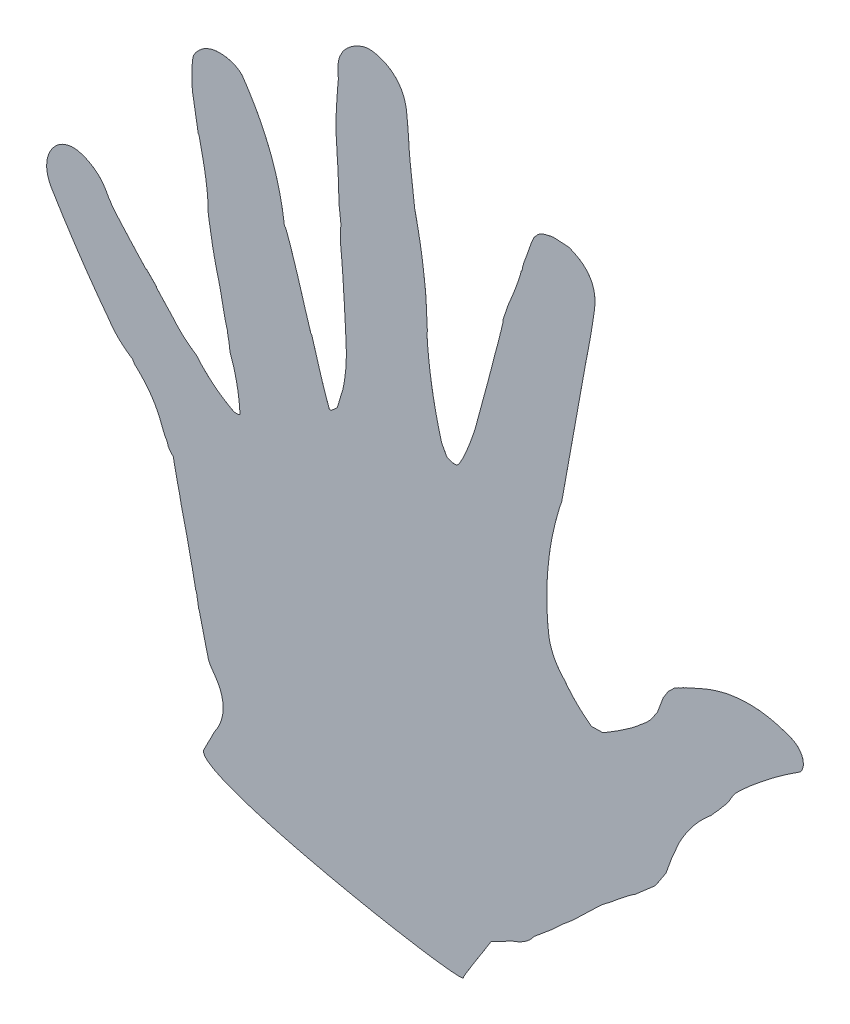
SolidWorks part; units mm, degrees
ref_plane "Plan de face" through (0, 0, 0) normal (0, 0, 1) x (1, 0, 0)
ref_plane "Plan de dessus" through (0, 0, 0) normal (0, 1, 0) x (1, 0, 0)
ref_plane "Plan de droite" through (0, 0, 0) normal (1, 0, 0) x (0, 0, -1)
sketch "Model" plane through (0, 0, 0) normal (0, 0, 1) x (1, 0, 0)
  line L0 (126.0092, -67.0317) -> (126.0337, -67.1279)
  line L1 (126.0337, -67.1279) -> (126.0791, -67.3399)
  line L2 (126.0791, -67.3399) -> (126.1236, -67.4942)
  line L3 (126.1236, -67.4942) -> (126.1236, -67.5328)
  line L4 (126.1236, -67.5328) -> (126.1477, -67.5707)
  line L5 (126.1477, -67.5707) -> (126.1477, -67.5907)
  line L6 (126.1477, -67.5907) -> (126.169, -67.6102)
  line L7 (126.169, -67.6102) -> (126.1477, -67.5707)
  line L8 (126.1477, -67.5707) -> (126.1477, -67.5523)
  line L9 (126.1477, -67.5523) -> (126.1236, -67.5137)
  line L10 (126.1236, -67.5137) -> (126.1236, -67.4942)
  line L11 (126.1236, -67.4942) -> (126.1236, -67.4364)
  line L12 (126.1236, -67.4364) -> (126.0791, -67.3399)
  line L13 (126.0791, -67.3399) -> (126.055, -67.2626)
  line L14 (126.055, -67.2626) -> (126.0092, -67.0317)
  line L15 (180.2508, -38.7148) -> (180.2967, -38.0785)
  line L16 (180.2967, -38.0785) -> (180.3645, -37.4801)
  line L17 (180.3645, -37.4801) -> (180.3893, -36.8825)
  line L18 (180.3893, -36.8825) -> (180.4117, -36.3227)
  line L19 (180.4117, -36.3227) -> (180.3893, -35.7444)
  line L20 (180.3893, -35.7444) -> (180.3645, -35.2046)
  line L21 (180.3645, -35.2046) -> (180.2508, -34.144)
  line L22 (180.2508, -34.144) -> (180.0228, -33.1213)
  line L23 (180.0228, -33.1213) -> (179.8629, -32.6199)
  line L24 (179.8629, -32.6199) -> (179.7258, -32.1567)
  line L25 (179.7258, -32.1567) -> (179.5208, -31.6746)
  line L26 (179.5208, -31.6746) -> (179.3155, -31.231)
  line L27 (179.3155, -31.231) -> (179.0871, -30.7874)
  line L28 (179.0871, -30.7874) -> (178.8594, -30.3826)
  line L29 (178.8594, -30.3826) -> (178.2644, -29.5525)
  line L30 (178.2644, -29.5525) -> (177.9454, -29.1476)
  line L31 (177.9454, -29.1476) -> (177.6257, -28.7814)
  line L32 (177.6257, -28.7814) -> (177.2381, -28.3957)
  line L33 (177.2381, -28.3957) -> (176.8729, -28.0481)
  line L34 (176.8729, -28.0481) -> (176.4623, -27.7008)
  line L35 (176.4623, -27.7008) -> (176.0499, -27.3926)
  line L36 (176.0499, -27.3926) -> (175.571, -27.0642)
  line L37 (175.571, -27.0642) -> (175.1149, -26.7748)
  line L38 (175.1149, -26.7748) -> (174.111, -26.216)
  line L39 (174.111, -26.216) -> (173.0148, -25.6949)
  line L40 (173.0148, -25.6949) -> (172.4212, -25.4439)
  line L41 (172.4212, -25.4439) -> (171.851, -25.2319)
  line L42 (171.851, -25.2319) -> (166.8735, -24.9425)
  line L43 (166.8735, -24.9425) -> (165.9837, -25.1163)
  line L44 (165.9837, -25.1163) -> (165.0483, -25.3282)
  line L45 (165.0483, -25.3282) -> (164.1571, -25.5602)
  line L46 (164.1571, -25.5602) -> (163.7692, -25.6758)
  line L47 (163.7692, -25.6758) -> (163.4498, -25.8103)
  line L48 (163.4498, -25.8103) -> (162.8796, -26.0425)
  line L49 (162.8796, -26.0425) -> (162.6726, -26.1579)
  line L50 (162.6726, -26.1579) -> (162.5127, -26.2928)
  line L51 (162.5127, -26.2928) -> (161.9884, -26.6015)
  line L52 (161.9884, -26.6015) -> (160.7092, -28.0681)
  line L53 (160.7092, -28.0681) -> (160.2528, -29.0511)
  line L54 (160.2528, -29.0511) -> (159.7739, -30.1315)
  line L55 (159.7739, -30.1315) -> (159.5689, -30.672)
  line L56 (159.5689, -30.672) -> (159.3863, -31.1926)
  line L57 (159.3863, -31.1926) -> (159.2037, -31.6746)
  line L58 (159.2037, -31.6746) -> (159.0669, -32.1376)
  line L59 (159.0669, -32.1376) -> (158.9071, -32.5611)
  line L60 (158.9071, -32.5611) -> (158.7703, -32.9668)
  line L61 (158.7703, -32.9668) -> (158.6318, -33.333)
  line L62 (158.6318, -33.333) -> (158.5405, -33.6806)
  line L63 (158.5405, -33.6806) -> (158.4034, -33.9895)
  line L64 (158.4034, -33.9895) -> (158.3125, -34.2787)
  line L65 (158.3125, -34.2787) -> (158.2212, -34.5297)
  line L66 (158.2212, -34.5297) -> (158.1526, -34.7607)
  line L67 (158.1526, -34.7607) -> (158.0617, -34.9539)
  line L68 (158.0617, -34.9539) -> (157.9931, -35.1274)
  line L69 (157.9931, -35.1274) -> (157.9473, -35.2618)
  line L70 (157.9473, -35.2618) -> (157.9246, -35.378)
  line L71 (157.9246, -35.378) -> (157.5139, -36.3811)
  line L72 (157.5139, -36.3811) -> (157.1945, -37.4036)
  line L73 (157.1945, -37.4036) -> (156.921, -38.4445)
  line L74 (156.921, -38.4445) -> (156.7611, -39.5056)
  line L75 (156.7611, -39.5056) -> (156.5317, -39.545)
  line L76 (156.5317, -39.545) -> (156.4645, -39.7759)
  line L77 (156.4645, -39.7759) -> (156.396, -40.0651)
  line L78 (156.396, -40.0651) -> (156.3033, -40.3732)
  line L79 (156.3033, -40.3732) -> (156.2347, -40.721)
  line L80 (156.2347, -40.721) -> (156.121, -41.0679)
  line L81 (156.121, -41.0679) -> (156.0067, -41.4543)
  line L82 (156.0067, -41.4543) -> (155.8699, -41.8596)
  line L83 (155.8699, -41.8596) -> (155.7559, -42.3218)
  line L84 (155.7559, -42.3218) -> (155.5733, -42.766)
  line L85 (155.5733, -42.766) -> (155.4138, -43.2671)
  line L86 (155.4138, -43.2671) -> (155.2312, -43.7689)
  line L87 (155.2312, -43.7689) -> (155.0486, -44.3275)
  line L88 (155.0486, -44.3275) -> (154.8205, -44.8875)
  line L89 (154.8205, -44.8875) -> (154.6152, -45.4849)
  line L90 (154.6152, -45.4849) -> (154.3627, -46.1033)
  line L91 (154.3627, -46.1033) -> (154.1346, -46.7586)
  line L92 (154.1346, -46.7586) -> (153.6099, -48.032)
  line L93 (153.6099, -48.032) -> (153.108, -49.2857)
  line L94 (153.108, -49.2857) -> (152.606, -50.462)
  line L95 (152.606, -50.462) -> (152.1258, -51.6194)
  line L96 (152.1258, -51.6194) -> (150.6199, -56.2298)
  line L97 (150.6199, -56.2298) -> (150.6427, -56.8275)
  line L98 (150.6427, -56.8275) -> (150.5059, -57.3095)
  line L99 (150.5059, -57.3095) -> (150.3691, -57.9076)
  line L100 (150.3691, -57.9076) -> (150.2778, -58.2355)
  line L101 (150.2778, -58.2355) -> (150.2093, -58.6014)
  line L102 (150.2093, -58.6014) -> (150.0253, -59.4124)
  line L103 (150.0253, -59.4124) -> (149.7972, -60.2804)
  line L104 (149.7972, -60.2804) -> (149.6601, -60.7432)
  line L105 (149.6601, -60.7432) -> (149.5461, -61.2638)
  line L106 (149.5461, -61.2638) -> (149.2725, -62.3442)
  line L107 (149.2725, -62.3442) -> (148.9987, -63.5401)
  line L108 (148.9987, -63.5401) -> (148.8161, -64.1385)
  line L109 (148.8161, -64.1385) -> (148.6566, -64.7938)
  line L110 (148.6566, -64.7938) -> (148.2914, -66.1636)
  line L111 (148.2914, -66.1636) -> (148.0861, -66.8576)
  line L112 (148.0861, -66.8576) -> (147.9038, -67.6102)
  line L113 (147.9038, -67.6102) -> (147.6981, -68.3619)
  line L114 (147.6981, -68.3619) -> (147.5159, -69.1722)
  line L115 (147.5159, -69.1722) -> (147.2861, -69.963)
  line L116 (147.2861, -69.963) -> (147.0808, -70.8115)
  line L117 (147.0808, -70.8115) -> (146.6246, -72.5671)
  line L118 (146.6246, -72.5671) -> (146.3738, -73.4541)
  line L119 (146.3738, -73.4541) -> (146.1458, -74.3998)
  line L120 (146.1458, -74.3998) -> (145.6421, -76.3473)
  line L121 (145.6421, -76.3473) -> (144.57, -80.2444)
  line L122 (144.57, -80.2444) -> (143.5433, -84.0629)
  line L123 (143.5433, -84.0629) -> (143.04, -85.9346)
  line L124 (143.04, -85.9346) -> (142.5381, -87.7859)
  line L125 (142.5381, -87.7859) -> (141.5573, -91.4509)
  line L126 (141.5573, -91.4509) -> (140.7115, -93.9584)
  line L127 (140.7115, -93.9584) -> (139.7992, -96.4661)
  line L128 (139.7992, -96.4661) -> (139.2973, -97.701)
  line L129 (139.2973, -97.701) -> (138.7936, -98.9547)
  line L130 (138.7936, -98.9547) -> (138.2462, -100.1891)
  line L131 (138.2462, -100.1891) -> (137.9723, -100.8059)
  line L132 (137.9723, -100.8059) -> (137.8355, -101.1146)
  line L133 (137.8355, -101.1146) -> (137.7673, -101.2693)
  line L134 (137.7673, -101.2693) -> (137.7215, -101.4429)
  line L135 (137.7215, -101.4429) -> (136.5564, -103.5065)
  line L136 (136.5564, -103.5065) -> (136.2601, -103.8924)
  line L137 (136.2601, -103.8924) -> (136.032, -104.2012)
  line L138 (136.032, -104.2012) -> (135.9176, -104.3161)
  line L139 (135.9176, -104.3161) -> (135.8263, -104.4124)
  line L140 (135.8263, -104.4124) -> (135.735, -104.4904)
  line L141 (135.735, -104.4904) -> (135.6896, -104.5488)
  line L142 (135.6896, -104.5488) -> (135.4615, -104.6253)
  line L143 (135.4615, -104.6253) -> (135.3929, -104.6253)
  line L144 (135.3929, -104.6253) -> (135.3475, -104.6453)
  line L145 (135.3475, -104.6453) -> (135.2562, -104.6832)
  line L146 (135.2562, -104.6832) -> (135.1194, -104.6832)
  line L147 (135.1194, -104.6832) -> (135.0508, -104.6832)
  line L148 (135.0508, -104.6832) -> (135.005, -104.7023)
  line L149 (135.005, -104.7023) -> (134.8686, -104.7023)
  line L150 (134.8686, -104.7023) -> (134.7983, -104.7023)
  line L151 (134.7983, -104.7023) -> (134.7542, -104.7216)
  line L152 (134.7542, -104.7216) -> (134.4562, -104.6832)
  line L153 (134.4562, -104.6832) -> (134.1827, -104.6453)
  line L154 (134.1827, -104.6453) -> (133.8633, -104.5673)
  line L155 (133.8633, -104.5673) -> (133.5436, -104.4708)
  line L156 (133.5436, -104.4708) -> (133.3155, -104.3745)
  line L157 (133.3155, -104.3745) -> (133.1102, -104.2975)
  line L158 (133.1102, -104.2975) -> (132.8822, -104.1818)
  line L159 (132.8822, -104.1818) -> (132.8122, -104.1432)
  line L160 (132.8122, -104.1432) -> (132.7681, -104.1235)
  line L161 (132.7681, -104.1235) -> (132.6755, -104.0853)
  line L162 (132.6755, -104.0853) -> (132.3344, -103.8924)
  line L163 (132.3344, -103.8924) -> (130.6449, -100.7675)
  line L164 (130.6449, -100.7675) -> (129.6855, -97.1026)
  line L165 (129.6855, -97.1026) -> (128.8414, -93.4763)
  line L166 (128.8414, -93.4763) -> (128.0869, -89.8495)
  line L167 (128.0869, -89.8495) -> (127.4479, -86.2812)
  line L168 (127.4479, -86.2812) -> (126.9004, -82.713)
  line L169 (126.9004, -82.713) -> (126.467, -79.1835)
  line L170 (126.467, -79.1835) -> (126.1236, -75.672)
  line L171 (126.1236, -75.672) -> (125.8955, -72.2004)
  line L172 (125.8955, -72.2004) -> (126.055, -71.9691)
  line L173 (126.055, -71.9691) -> (125.5985, -62.652)
  line L174 (125.5985, -62.652) -> (125.3477, -59.9135)
  line L175 (125.3477, -59.9135) -> (125.0511, -57.387)
  line L176 (125.0511, -57.387) -> (124.7317, -54.8795)
  line L177 (124.7317, -54.8795) -> (124.3897, -52.3722)
  line L178 (124.3897, -52.3722) -> (124.0017, -49.8831)
  line L179 (124.0017, -49.8831) -> (123.567, -47.3756)
  line L180 (123.567, -47.3756) -> (123.0879, -44.8875)
  line L181 (123.0879, -44.8875) -> (122.586, -42.399)
  line L182 (122.586, -42.399) -> (122.0596, -39.9306)
  line L183 (122.0596, -39.9306) -> (122.0141, -39.8722)
  line L184 (122.0141, -39.8722) -> (122.0141, -39.8143)
  line L185 (122.0141, -39.8143) -> (121.9929, -39.7759)
  line L186 (121.9929, -39.7759) -> (121.9929, -39.7567)
  line L187 (121.9929, -39.7567) -> (121.9929, -39.718)
  line L188 (121.9929, -39.718) -> (121.9929, -39.6021)
  line L189 (121.9929, -39.6021) -> (121.9457, -39.4486)
  line L190 (121.9457, -39.4486) -> (121.9228, -39.409)
  line L191 (121.9228, -39.409) -> (121.9228, -39.3902)
  line L192 (121.9228, -39.3902) -> (121.9228, -39.3521)
  line L193 (121.9228, -39.3521) -> (121.9228, -39.2743)
  line L194 (121.9228, -39.2743) -> (121.8787, -39.0624)
  line L195 (121.8787, -39.0624) -> (121.8787, -38.8302)
  line L196 (121.8787, -38.8302) -> (121.7647, -37.9625)
  line L197 (121.7647, -37.9625) -> (121.672, -37.1908)
  line L198 (121.672, -37.1908) -> (121.6263, -36.8446)
  line L199 (121.6263, -36.8446) -> (121.5822, -36.4775)
  line L200 (121.5822, -36.4775) -> (121.4894, -35.7062)
  line L201 (121.4894, -35.7062) -> (121.4453, -35.4745)
  line L202 (121.4453, -35.4745) -> (121.4208, -35.3584)
  line L203 (121.4208, -35.3584) -> (121.4208, -35.2618)
  line L204 (121.4208, -35.2618) -> (121.3752, -34.8189)
  line L205 (121.3752, -34.8189) -> (121.2839, -33.8928)
  line L206 (121.2839, -33.8928) -> (121.1471, -32.8509)
  line L207 (121.1471, -32.8509) -> (121.0787, -32.3114)
  line L208 (121.0787, -32.3114) -> (121.0331, -31.7517)
  line L209 (121.0331, -31.7517) -> (120.942, -31.154)
  line L210 (120.942, -31.154) -> (120.8963, -30.8453)
  line L211 (120.8963, -30.8453) -> (120.8734, -30.691)
  line L212 (120.8734, -30.691) -> (120.8734, -30.5556)
  line L213 (120.8734, -30.5556) -> (120.7365, -29.2825)
  line L214 (120.7365, -29.2825) -> (120.5752, -28.1061)
  line L215 (120.5752, -28.1061) -> (120.4614, -26.9875)
  line L216 (120.4614, -26.9875) -> (120.3487, -25.9266)
  line L217 (120.3487, -25.9266) -> (120.2574, -24.9234)
  line L218 (120.2574, -24.9234) -> (120.1663, -23.9395)
  line L219 (120.1663, -23.9395) -> (120.0978, -23.0334)
  line L220 (120.0978, -23.0334) -> (120.0294, -22.1652)
  line L221 (120.0294, -22.1652) -> (120.0065, -21.3551)
  line L222 (120.0065, -21.3551) -> (119.8452, -19.1756)
  line L223 (119.8452, -19.1756) -> (119.6628, -17.0152)
  line L224 (119.6628, -17.0152) -> (119.4577, -14.8551)
  line L225 (119.4577, -14.8551) -> (119.2065, -12.7136)
  line L226 (119.2065, -12.7136) -> (118.9784, -11.6329)
  line L227 (118.9784, -11.6329) -> (118.7046, -10.5723)
  line L228 (118.7046, -10.5723) -> (118.5221, -10.0326)
  line L229 (118.5221, -10.0326) -> (118.317, -9.5307)
  line L230 (118.317, -9.5307) -> (117.8607, -8.5278)
  line L231 (117.8607, -8.5278) -> (117.5184, -7.9299)
  line L232 (117.5184, -7.9299) -> (117.152, -7.3704)
  line L233 (117.152, -7.3704) -> (116.7641, -6.8302)
  line L234 (116.7641, -6.8302) -> (116.3764, -6.3483)
  line L235 (116.3764, -6.3483) -> (115.9201, -5.8463)
  line L236 (115.9201, -5.8463) -> (115.4622, -5.4038)
  line L237 (115.4622, -5.4038) -> (114.983, -4.9783)
  line L238 (114.983, -4.9783) -> (114.5041, -4.5925)
  line L239 (114.5041, -4.5925) -> (113.9565, -4.188)
  line L240 (113.9565, -4.188) -> (113.4091, -3.8408)
  line L241 (113.4091, -3.8408) -> (112.8372, -3.5126)
  line L242 (112.8372, -3.5126) -> (112.2441, -3.2234)
  line L243 (112.2441, -3.2234) -> (111.6054, -2.934)
  line L244 (111.6054, -2.934) -> (110.9424, -2.7032)
  line L245 (110.9424, -2.7032) -> (110.2579, -2.4707)
  line L246 (110.2579, -2.4707) -> (109.5735, -2.2977)
  line L247 (109.5735, -2.2977) -> (108.8435, -2.1244)
  line L248 (108.8435, -2.1244) -> (108.1348, -2.028)
  line L249 (108.1348, -2.028) -> (107.4276, -1.9885)
  line L250 (107.4276, -1.9885) -> (106.7432, -2.028)
  line L251 (106.7432, -2.028) -> (106.0571, -2.0848)
  line L252 (106.0571, -2.0848) -> (105.3956, -2.2397)
  line L253 (105.3956, -2.2397) -> (104.734, -2.4324)
  line L254 (104.734, -2.4324) -> (104.0939, -2.7032)
  line L255 (104.0939, -2.7032) -> (103.0671, -3.1654)
  line L256 (103.0671, -3.1654) -> (102.1547, -3.6863)
  line L257 (102.1547, -3.6863) -> (101.3091, -4.2463)
  line L258 (101.3091, -4.2463) -> (100.5563, -4.8436)
  line L259 (100.5563, -4.8436) -> (99.849, -5.4801)
  line L260 (99.849, -5.4801) -> (99.2317, -6.1554)
  line L261 (99.2317, -6.1554) -> (98.6841, -6.869)
  line L262 (98.6841, -6.869) -> (98.2278, -7.6602)
  line L263 (98.2278, -7.6602) -> (97.8173, -8.4505)
  line L264 (97.8173, -8.4505) -> (97.6331, -8.856)
  line L265 (97.6331, -8.856) -> (97.4962, -9.2995)
  line L266 (97.4962, -9.2995) -> (97.2454, -10.1677)
  line L267 (97.2454, -10.1677) -> (97.1086, -11.1127)
  line L268 (97.1086, -11.1127) -> (96.9944, -12.0582)
  line L269 (96.9944, -12.0582) -> (96.9944, -13.0795)
  line L270 (96.9944, -13.0795) -> (96.9944, -13.5813)
  line L271 (96.9944, -13.5813) -> (97.0401, -14.1218)
  line L272 (97.0401, -14.1218) -> (97.1998, -15.2211)
  line L273 (97.1998, -15.2211) -> (96.926, -18.191)
  line L274 (96.926, -18.191) -> (96.7205, -21.162)
  line L275 (96.7205, -21.162) -> (96.5381, -24.0938)
  line L276 (96.5381, -24.0938) -> (96.4241, -27.007)
  line L277 (96.4241, -27.007) -> (96.3555, -28.4341)
  line L278 (96.3555, -28.4341) -> (96.3784, -29.8809)
  line L279 (96.3784, -29.8809) -> (96.4468, -31.3275)
  line L280 (96.4468, -31.3275) -> (96.561, -32.794)
  line L281 (96.561, -32.794) -> (96.6523, -34.3171)
  line L282 (96.6523, -34.3171) -> (96.7434, -35.9182)
  line L283 (96.7434, -35.9182) -> (96.8347, -37.5763)
  line L284 (96.8347, -37.5763) -> (96.9717, -39.3321)
  line L285 (96.9717, -39.3321) -> (96.9944, -40.1805)
  line L286 (96.9944, -40.1805) -> (97.0401, -41.0108)
  line L287 (97.0401, -41.0108) -> (97.0855, -41.8202)
  line L288 (97.0855, -41.8202) -> (97.1327, -42.6115)
  line L289 (97.1327, -42.6115) -> (97.1541, -43.3445)
  line L290 (97.1541, -43.3445) -> (97.1998, -44.0776)
  line L291 (97.1998, -44.0776) -> (97.2225, -44.7716)
  line L292 (97.2225, -44.7716) -> (97.2697, -45.447)
  line L293 (97.2697, -45.447) -> (97.2697, -46.064)
  line L294 (97.2697, -46.064) -> (97.291, -46.6816)
  line L295 (97.291, -46.6816) -> (97.291, -47.2605)
  line L296 (97.291, -47.2605) -> (97.3367, -47.8195)
  line L297 (97.3367, -47.8195) -> (97.3367, -48.34)
  line L298 (97.3367, -48.34) -> (97.3367, -48.8415)
  line L299 (97.3367, -48.8415) -> (97.3367, -49.3047)
  line L300 (97.3367, -49.3047) -> (97.3367, -49.517)
  line L301 (97.3367, -49.517) -> (97.361, -49.7482)
  line L302 (97.361, -49.7482) -> (97.361, -49.8831)
  line L303 (97.361, -49.8831) -> (97.361, -50.0953)
  line L304 (97.361, -50.0953) -> (97.3823, -50.3657)
  line L305 (97.3823, -50.3657) -> (97.428, -50.7323)
  line L306 (97.428, -50.7323) -> (97.4752, -51.1183)
  line L307 (97.4752, -51.1183) -> (97.5191, -51.6005)
  line L308 (97.5191, -51.6005) -> (97.5875, -52.121)
  line L309 (97.5875, -52.121) -> (97.6803, -52.7379)
  line L310 (97.6803, -52.7379) -> (97.7244, -53.3365)
  line L311 (97.7244, -53.3365) -> (97.7473, -53.606)
  line L312 (97.7473, -53.606) -> (97.793, -53.8758)
  line L313 (97.793, -53.8758) -> (97.8402, -54.3579)
  line L314 (97.8402, -54.3579) -> (97.8402, -54.4544)
  line L315 (97.8402, -54.4544) -> (97.8612, -54.5705)
  line L316 (97.8612, -54.5705) -> (97.9084, -54.802)
  line L317 (97.9084, -54.802) -> (97.9084, -54.9761)
  line L318 (97.9084, -54.9761) -> (97.9298, -55.1689)
  line L319 (97.9298, -55.1689) -> (97.9754, -55.4772)
  line L320 (97.9754, -55.4772) -> (97.9754, -55.728)
  line L321 (97.9754, -55.728) -> (97.9754, -55.8245)
  line L322 (97.9754, -55.8245) -> (97.9982, -55.9404)
  line L323 (97.9982, -55.9404) -> (97.9982, -55.9974)
  line L324 (97.9982, -55.9974) -> (97.8612, -57.6182)
  line L325 (97.8612, -57.6182) -> (97.8173, -59.2577)
  line L326 (97.8173, -59.2577) -> (97.8612, -60.8971)
  line L327 (97.8612, -60.8971) -> (98.0211, -62.5555)
  line L328 (98.0211, -62.5555) -> (98.0683, -63.2308)
  line L329 (98.0683, -63.2308) -> (98.1596, -63.9837)
  line L330 (98.1596, -63.9837) -> (98.2052, -64.755)
  line L331 (98.2052, -64.755) -> (98.2963, -65.585)
  line L332 (98.2963, -65.585) -> (98.3418, -66.4332)
  line L333 (98.3418, -66.4332) -> (98.4331, -67.3399)
  line L334 (98.4331, -67.3399) -> (98.5017, -68.2854)
  line L335 (98.5017, -68.2854) -> (98.5928, -69.2881)
  line L336 (98.5928, -69.2881) -> (98.6384, -70.3104)
  line L337 (98.6384, -70.3104) -> (98.7297, -71.3717)
  line L338 (98.7297, -71.3717) -> (98.7981, -72.4705)
  line L339 (98.7981, -72.4705) -> (98.8894, -73.647)
  line L340 (98.8894, -73.647) -> (98.9349, -74.8239)
  line L341 (98.9349, -74.8239) -> (99.0262, -76.0775)
  line L342 (99.0262, -76.0775) -> (99.1175, -77.3514)
  line L343 (99.1175, -77.3514) -> (99.2088, -78.6817)
  line L344 (99.2088, -78.6817) -> (99.2544, -79.9934)
  line L345 (99.2544, -79.9934) -> (99.3455, -81.2856)
  line L346 (99.3455, -81.2856) -> (99.3912, -82.5395)
  line L347 (99.3912, -82.5395) -> (99.4825, -83.7932)
  line L348 (99.4825, -83.7932) -> (99.5297, -84.989)
  line L349 (99.5297, -84.989) -> (99.5526, -85.5681)
  line L350 (99.5526, -85.5681) -> (99.5967, -86.166)
  line L351 (99.5967, -86.166) -> (99.6423, -87.3041)
  line L352 (99.6423, -87.3041) -> (99.6423, -87.5745)
  line L353 (99.6423, -87.5745) -> (99.6423, -87.7089)
  line L354 (99.6423, -87.7089) -> (99.6666, -87.8637)
  line L355 (99.6666, -87.8637) -> (99.7105, -88.4421)
  line L356 (99.7105, -88.4421) -> (99.7352, -89.2905)
  line L357 (99.7352, -89.2905) -> (99.7352, -89.7149)
  line L358 (99.7352, -89.7149) -> (99.7352, -89.9273)
  line L359 (99.7352, -89.9273) -> (99.7577, -90.1587)
  line L360 (99.7577, -90.1587) -> (99.7791, -91.8561)
  line L361 (99.7791, -91.8561) -> (99.7352, -92.6855)
  line L362 (99.7352, -92.6855) -> (99.7105, -93.5345)
  line L363 (99.7105, -93.5345) -> (99.6423, -95.1932)
  line L364 (99.6423, -95.1932) -> (99.4597, -96.8132)
  line L365 (99.4597, -96.8132) -> (99.2544, -98.4725)
  line L366 (99.2544, -98.4725) -> (98.9805, -100.1312)
  line L367 (98.9805, -100.1312) -> (98.6598, -101.8284)
  line L368 (98.6598, -101.8284) -> (98.4789, -102.3304)
  line L369 (98.4789, -102.3304) -> (96.8118, -107.9242)
  line L370 (96.8118, -107.9242) -> (94.8256, -109.6405)
  line L371 (94.8256, -109.6405) -> (94.5748, -109.66)
  line L372 (94.5748, -109.66) -> (94.4151, -109.6405)
  line L373 (94.4151, -109.6405) -> (94.301, -109.5826)
  line L374 (94.301, -109.5826) -> (94.2325, -109.5055)
  line L375 (94.2325, -109.5055) -> (94.0501, -109.0621)
  line L376 (94.0501, -109.0621) -> (93.8904, -108.5994)
  line L377 (93.8904, -108.5994) -> (93.708, -108.0775)
  line L378 (93.708, -108.0775) -> (93.5238, -107.5574)
  line L379 (93.5238, -107.5574) -> (93.2958, -106.9787)
  line L380 (93.2958, -106.9787) -> (93.1132, -106.3811)
  line L381 (93.1132, -106.3811) -> (92.8851, -105.7443)
  line L382 (92.8851, -105.7443) -> (92.6796, -105.0878)
  line L383 (92.6796, -105.0878) -> (92.543, -104.7216)
  line L384 (92.543, -104.7216) -> (92.4288, -104.3745)
  line L385 (92.4288, -104.3745) -> (92.2007, -103.6223)
  line L386 (92.2007, -103.6223) -> (91.9269, -102.8314)
  line L387 (91.9269, -102.8314) -> (91.6988, -102.0413)
  line L388 (91.6988, -102.0413) -> (91.4251, -101.1919)
  line L389 (91.4251, -101.1919) -> (91.1496, -100.3238)
  line L390 (91.1496, -100.3238) -> (90.8759, -99.4172)
  line L391 (90.8759, -99.4172) -> (90.6022, -98.4725)
  line L392 (90.6022, -98.4725) -> (88.5021, -91.4318)
  line L393 (88.5021, -91.4318) -> (88.2739, -91.3353)
  line L394 (88.2739, -91.3353) -> (87.6122, -89.2138)
  line L395 (87.6122, -89.2138) -> (86.9964, -87.2269)
  line L396 (86.9964, -87.2269) -> (86.4016, -85.3168)
  line L397 (86.4016, -85.3168) -> (85.8771, -83.5234)
  line L398 (85.8771, -83.5234) -> (85.3522, -81.8065)
  line L399 (85.3522, -81.8065) -> (84.8732, -80.2246)
  line L400 (84.8732, -80.2246) -> (84.4155, -78.7201)
  line L401 (84.4155, -78.7201) -> (84.0049, -77.3314)
  line L402 (84.0049, -77.3314) -> (83.5927, -76.0775)
  line L403 (83.5927, -76.0775) -> (83.2292, -74.9201)
  line L404 (83.2292, -74.9201) -> (82.8642, -73.8208)
  line L405 (82.8642, -73.8208) -> (82.5431, -72.7987)
  line L406 (82.5431, -72.7987) -> (82.2237, -71.8146)
  line L407 (82.2237, -71.8146) -> (81.9273, -70.9275)
  line L408 (81.9273, -70.9275) -> (81.6536, -70.0982)
  line L409 (81.6536, -70.0982) -> (81.4024, -69.3465)
  line L410 (81.4024, -69.3465) -> (81.1516, -68.6316)
  line L411 (81.1516, -68.6316) -> (80.9236, -67.9962)
  line L412 (80.9236, -67.9962) -> (80.7181, -67.4172)
  line L413 (80.7181, -67.4172) -> (80.5357, -66.9353)
  line L414 (80.5357, -66.9353) -> (80.3517, -66.4719)
  line L415 (80.3517, -66.4719) -> (80.1936, -66.1052)
  line L416 (80.1936, -66.1052) -> (80.0551, -65.7968)
  line L417 (80.0551, -65.7968) -> (79.9412, -65.585)
  line L418 (79.9412, -65.585) -> (79.6916, -65.4492)
  line L419 (79.6916, -65.4492) -> (79.348, -63.0382)
  line L420 (79.348, -63.0382) -> (78.96, -60.6854)
  line L421 (78.96, -60.6854) -> (78.481, -58.332)
  line L422 (78.481, -58.332) -> (77.9548, -56.0365)
  line L423 (77.9548, -56.0365) -> (77.3388, -53.7409)
  line L424 (77.3388, -53.7409) -> (76.6773, -51.4842)
  line L425 (76.6773, -51.4842) -> (75.9244, -49.2278)
  line L426 (75.9244, -49.2278) -> (75.1244, -47.0283)
  line L427 (75.1244, -47.0283) -> (74.212, -44.81)
  line L428 (74.212, -44.81) -> (73.2522, -42.6501)
  line L429 (73.2522, -42.6501) -> (72.2257, -40.4897)
  line L430 (72.2257, -40.4897) -> (71.1521, -38.3877)
  line L431 (71.1521, -38.3877) -> (69.9885, -36.2844)
  line L432 (69.9885, -36.2844) -> (68.755, -34.2205)
  line L433 (68.755, -34.2205) -> (67.4548, -32.1567)
  line L434 (67.4548, -32.1567) -> (66.1074, -30.1506)
  line L435 (66.1074, -30.1506) -> (65.6725, -29.6681)
  line L436 (65.6725, -29.6681) -> (65.2162, -29.2633)
  line L437 (65.2162, -29.2633) -> (64.7142, -28.8969)
  line L438 (64.7142, -28.8969) -> (64.1895, -28.5691)
  line L439 (64.1895, -28.5691) -> (63.6192, -28.2799)
  line L440 (63.6192, -28.2799) -> (63.0017, -28.0288)
  line L441 (63.0017, -28.0288) -> (62.3628, -27.8167)
  line L442 (62.3628, -27.8167) -> (61.7013, -27.6429)
  line L443 (61.7013, -27.6429) -> (60.8118, -27.45)
  line L444 (60.8118, -27.45) -> (59.966, -27.3348)
  line L445 (59.966, -27.3348) -> (59.122, -27.2767)
  line L446 (59.122, -27.2767) -> (58.3463, -27.2767)
  line L447 (58.3463, -27.2767) -> (57.5465, -27.3151)
  line L448 (57.5465, -27.3151) -> (56.8165, -27.4312)
  line L449 (56.8165, -27.4312) -> (56.0848, -27.5859)
  line L450 (56.0848, -27.5859) -> (55.4004, -27.8167)
  line L451 (55.4004, -27.8167) -> (54.6933, -28.0681)
  line L452 (54.6933, -28.0681) -> (54.053, -28.3957)
  line L453 (54.053, -28.3957) -> (53.4143, -28.7617)
  line L454 (53.4143, -28.7617) -> (52.8211, -29.2055)
  line L455 (52.8211, -29.2055) -> (52.2264, -29.6881)
  line L456 (52.2264, -29.6881) -> (51.6788, -30.2278)
  line L457 (51.6788, -30.2278) -> (51.1314, -30.8255)
  line L458 (51.1314, -30.8255) -> (50.6524, -31.5007)
  line L459 (50.6524, -31.5007) -> (50.1961, -32.2917)
  line L460 (50.1961, -32.2917) -> (50.0593, -32.8319)
  line L461 (50.0593, -32.8319) -> (49.9437, -33.4688)
  line L462 (49.9437, -33.4688) -> (49.8524, -34.144)
  line L463 (49.8524, -34.144) -> (49.7854, -34.9155)
  line L464 (49.7854, -34.9155) -> (49.7157, -35.7251)
  line L465 (49.7157, -35.7251) -> (49.6927, -36.6317)
  line L466 (49.6927, -36.6317) -> (49.67, -37.5963)
  line L467 (49.67, -37.5963) -> (49.6927, -38.6374)
  line L468 (49.6927, -38.6374) -> (49.6927, -39.6603)
  line L469 (49.6927, -39.6603) -> (49.7398, -40.6632)
  line L470 (49.7398, -40.6632) -> (49.7854, -41.589)
  line L471 (49.7854, -41.589) -> (49.8524, -42.4953)
  line L472 (49.8524, -42.4953) -> (51.7474, -53.4712)
  line L473 (51.7474, -53.4712) -> (51.9526, -53.5866)
  line L474 (51.9526, -53.5866) -> (52.2736, -55.0912)
  line L475 (52.2736, -55.0912) -> (52.593, -56.5571)
  line L476 (52.593, -56.5571) -> (52.7298, -57.2511)
  line L477 (52.7298, -57.2511) -> (52.7982, -57.5987)
  line L478 (52.7982, -57.5987) -> (52.8881, -57.9658)
  line L479 (52.8881, -57.9658) -> (53.0262, -58.6407)
  line L480 (53.0262, -58.6407) -> (53.0493, -58.7947)
  line L481 (53.0493, -58.7947) -> (53.0948, -58.9685)
  line L482 (53.0948, -58.9685) -> (53.1861, -59.3161)
  line L483 (53.1861, -59.3161) -> (53.2317, -59.6244)
  line L484 (53.2317, -59.6244) -> (53.2545, -59.7786)
  line L485 (53.2545, -59.7786) -> (53.3001, -59.9514)
  line L486 (53.3001, -59.9514) -> (53.4369, -60.5889)
  line L487 (53.4369, -60.5889) -> (53.6667, -61.8038)
  line L488 (53.6667, -61.8038) -> (53.758, -62.3826)
  line L489 (53.758, -62.3826) -> (53.8704, -62.9612)
  line L490 (53.8704, -62.9612) -> (53.9633, -63.5202)
  line L491 (53.9633, -63.5202) -> (54.0074, -63.7909)
  line L492 (54.0074, -63.7909) -> (54.0074, -63.8488)
  line L493 (54.0074, -63.8488) -> (54.0301, -63.9256)
  line L494 (54.0301, -63.9256) -> (54.0773, -64.08)
  line L495 (54.0773, -64.08) -> (54.2826, -65.4689)
  line L496 (54.2826, -65.4689) -> (54.4652, -66.8388)
  line L497 (54.4652, -66.8388) -> (54.5336, -67.4942)
  line L498 (54.5336, -67.4942) -> (54.6247, -68.1691)
  line L499 (54.6247, -68.1691) -> (54.7617, -69.4998)
  line L500 (54.7617, -69.4998) -> (54.853, -70.7731)
  line L501 (54.853, -70.7731) -> (54.8759, -71.3905)
  line L502 (54.8759, -71.3905) -> (54.9215, -72.027)
  line L503 (54.9215, -72.027) -> (54.9672, -73.2424)
  line L504 (54.9672, -73.2424) -> (54.9672, -73.8398)
  line L505 (54.9672, -73.8398) -> (54.9898, -74.4576)
  line L506 (54.9898, -74.4576) -> (56.0166, -80.4945)
  line L507 (56.0166, -80.4945) -> (56.1533, -81.3055)
  line L508 (56.1533, -81.3055) -> (56.2917, -82.0959)
  line L509 (56.2917, -82.0959) -> (56.4272, -82.8485)
  line L510 (56.4272, -82.8485) -> (56.4272, -82.925)
  line L511 (56.4272, -82.925) -> (56.4513, -83.022)
  line L512 (56.4513, -83.022) -> (56.497, -83.2147)
  line L513 (56.497, -83.2147) -> (56.5883, -83.6002)
  line L514 (56.5883, -83.6002) -> (56.7252, -84.3142)
  line L515 (56.7252, -84.3142) -> (56.862, -85.0086)
  line L516 (56.862, -85.0086) -> (56.9989, -85.6644)
  line L517 (56.9989, -85.6644) -> (57.0673, -85.973)
  line L518 (57.0673, -85.973) -> (57.1584, -86.3007)
  line L519 (57.1584, -86.3007) -> (57.2041, -86.5901)
  line L520 (57.2041, -86.5901) -> (57.2726, -86.8991)
  line L521 (57.2726, -86.8991) -> (57.4096, -87.4777)
  line L522 (57.4096, -87.4777) -> (57.6833, -88.5577)
  line L523 (57.6833, -88.5577) -> (57.7746, -89.0592)
  line L524 (57.7746, -89.0592) -> (57.9115, -89.5411)
  line L525 (57.9115, -89.5411) -> (57.9572, -89.753)
  line L526 (57.9572, -89.753) -> (58.0254, -89.9854)
  line L527 (58.0254, -89.9854) -> (58.1639, -90.4286)
  line L528 (58.1639, -90.4286) -> (58.2781, -90.9686)
  line L529 (58.2781, -90.9686) -> (58.4376, -91.5856)
  line L530 (58.4376, -91.5856) -> (58.5959, -92.3)
  line L531 (58.5959, -92.3) -> (58.7797, -93.1099)
  line L532 (58.7797, -93.1099) -> (58.9623, -93.9781)
  line L533 (58.9623, -93.9781) -> (59.1661, -94.942)
  line L534 (59.1661, -94.942) -> (59.3728, -96.0029)
  line L535 (59.3728, -96.0029) -> (59.6239, -97.1605)
  line L536 (59.6239, -97.1605) -> (59.8065, -98.1833)
  line L537 (59.8065, -98.1833) -> (59.8976, -98.6655)
  line L538 (59.8976, -98.6655) -> (60.0117, -99.1666)
  line L539 (60.0117, -99.1666) -> (60.1941, -100.0926)
  line L540 (60.1941, -100.0926) -> (60.2854, -100.5167)
  line L541 (60.2854, -100.5167) -> (60.3326, -100.7289)
  line L542 (60.3326, -100.7289) -> (60.4011, -100.9602)
  line L543 (60.4011, -100.9602) -> (60.5836, -101.7516)
  line L544 (60.5836, -101.7516) -> (60.7661, -102.5033)
  line L545 (60.7661, -102.5033) -> (60.9486, -103.198)
  line L546 (60.9486, -103.198) -> (61.0399, -103.5065)
  line L547 (61.0399, -103.5065) -> (61.0855, -103.6607)
  line L548 (61.0855, -103.6607) -> (61.1082, -103.7375)
  line L549 (61.1082, -103.7375) -> (61.1539, -103.8341)
  line L550 (61.1539, -103.8341) -> (61.1995, -104.2197)
  line L551 (61.1995, -104.2197) -> (61.2452, -104.5867)
  line L552 (61.2452, -104.5867) -> (61.2907, -104.8951)
  line L553 (61.2907, -104.8951) -> (61.3348, -105.1653)
  line L554 (61.3348, -105.1653) -> (61.3348, -105.3581)
  line L555 (61.3348, -105.3581) -> (61.382, -105.5317)
  line L556 (61.382, -105.5317) -> (61.382, -105.6476)
  line L557 (61.382, -105.6476) -> (61.4276, -105.7443)
  line L558 (61.4276, -105.7443) -> (61.4733, -105.9176)
  line L559 (61.4733, -105.9176) -> (61.5189, -106.1298)
  line L560 (61.5189, -106.1298) -> (61.563, -106.3811)
  line L561 (61.563, -106.3811) -> (61.6331, -106.6701)
  line L562 (61.6331, -106.6701) -> (61.6788, -106.9595)
  line L563 (61.6788, -106.9595) -> (61.7242, -107.3257)
  line L564 (61.7242, -107.3257) -> (61.8612, -108.1167)
  line L565 (61.8612, -108.1167) -> (61.9523, -108.9267)
  line L566 (61.9523, -108.9267) -> (62.0434, -109.6787)
  line L567 (62.0434, -109.6787) -> (62.6823, -111.5117)
  line L568 (62.6823, -111.5117) -> (63.2754, -113.3819)
  line L569 (63.2754, -113.3819) -> (63.7789, -115.292)
  line L570 (63.7789, -115.292) -> (64.2352, -117.2793)
  line L571 (64.2352, -117.2793) -> (64.6002, -119.2652)
  line L572 (64.6002, -119.2652) -> (64.8968, -121.3103)
  line L573 (64.8968, -121.3103) -> (65.1263, -123.3742)
  line L574 (65.1263, -123.3742) -> (65.2861, -125.5152)
  line L575 (65.2861, -125.5152) -> (64.9667, -125.8235)
  line L576 (64.9667, -125.8235) -> (63.9597, -125.901)
  line L577 (63.9597, -125.901) -> (63.0718, -125.6702)
  line L578 (63.0718, -125.6702) -> (62.1805, -125.1682)
  line L579 (62.1805, -125.1682) -> (61.3348, -124.6856)
  line L580 (61.3348, -124.6856) -> (59.6696, -123.6445)
  line L581 (59.6696, -123.6445) -> (58.8483, -123.0848)
  line L582 (58.8483, -123.0848) -> (58.071, -122.5257)
  line L583 (58.071, -122.5257) -> (57.2954, -121.9276)
  line L584 (57.2954, -121.9276) -> (56.5654, -121.3488)
  line L585 (56.5654, -121.3488) -> (55.081, -120.0759)
  line L586 (55.081, -120.0759) -> (53.688, -118.7642)
  line L587 (53.688, -118.7642) -> (53.0037, -118.07)
  line L588 (53.0037, -118.07) -> (52.3648, -117.3756)
  line L589 (52.3648, -117.3756) -> (51.1087, -115.9288)
  line L590 (51.1087, -115.9288) -> (50.0137, -115.2147)
  line L591 (50.0137, -115.2147) -> (48.9856, -114.4628)
  line L592 (48.9856, -114.4628) -> (48.0045, -113.6911)
  line L593 (48.0045, -113.6911) -> (47.0678, -112.8999)
  line L594 (47.0678, -112.8999) -> (46.1324, -112.0516)
  line L595 (46.1324, -112.0516) -> (45.2882, -111.1834)
  line L596 (45.2882, -111.1834) -> (44.4428, -110.2959)
  line L597 (44.4428, -110.2959) -> (43.6898, -109.3899)
  line L598 (43.6898, -109.3899) -> (38.1188, -103.4099)
  line L599 (38.1188, -103.4099) -> (38.1188, -103.1401)
  line L600 (38.1188, -103.1401) -> (35.0606, -100.0347)
  line L601 (35.0606, -100.0347) -> (34.7638, -99.9762)
  line L602 (34.7638, -99.9762) -> (32.2285, -97.2378)
  line L603 (32.2285, -97.2378) -> (29.7177, -94.4792)
  line L604 (29.7177, -94.4792) -> (27.2068, -91.6823)
  line L605 (27.2068, -91.6823) -> (24.7416, -88.8664)
  line L606 (24.7416, -88.8664) -> (24.3081, -88.3264)
  line L607 (24.3081, -88.3264) -> (23.9188, -87.8055)
  line L608 (23.9188, -87.8055) -> (23.5309, -87.2653)
  line L609 (23.5309, -87.2653) -> (23.2113, -86.7253)
  line L610 (23.2113, -86.7253) -> (22.9833, -86.455)
  line L611 (22.9833, -86.455) -> (22.8008, -86.1849)
  line L612 (22.8008, -86.1849) -> (22.6183, -85.8954)
  line L613 (22.6183, -85.8954) -> (22.4813, -85.626)
  line L614 (22.4813, -85.626) -> (22.0937, -84.8737)
  line L615 (22.0937, -84.8737) -> (21.706, -84.1987)
  line L616 (21.706, -84.1987) -> (21.2709, -83.5234)
  line L617 (21.2709, -83.5234) -> (20.8375, -82.9055)
  line L618 (20.8375, -82.9055) -> (20.3583, -82.308)
  line L619 (20.3583, -82.308) -> (19.8563, -81.7483)
  line L620 (19.8563, -81.7483) -> (19.3075, -81.2092)
  line L621 (19.3075, -81.2092) -> (18.7601, -80.7267)
  line L622 (18.7601, -80.7267) -> (18.1439, -80.2444)
  line L623 (18.1439, -80.2444) -> (17.5266, -79.8196)
  line L624 (17.5266, -79.8196) -> (16.8648, -79.415)
  line L625 (16.8648, -79.415) -> (16.2033, -79.0479)
  line L626 (16.2033, -79.0479) -> (15.4733, -78.6817)
  line L627 (15.4733, -78.6817) -> (14.7417, -78.3923)
  line L628 (14.7417, -78.3923) -> (13.9661, -78.1032)
  line L629 (13.9661, -78.1032) -> (13.1904, -77.8903)
  line L630 (13.1904, -77.8903) -> (12.3222, -77.6976)
  line L631 (12.3222, -77.6976) -> (11.5009, -77.6206)
  line L632 (11.5009, -77.6206) -> (10.6796, -77.6404)
  line L633 (10.6796, -77.6404) -> (9.8568, -77.7749)
  line L634 (9.8568, -77.7749) -> (9.1267, -77.9298)
  line L635 (9.1267, -77.9298) -> (8.4653, -78.1415)
  line L636 (8.4653, -78.1415) -> (7.8021, -78.3923)
  line L637 (7.8021, -78.3923) -> (7.2089, -78.7201)
  line L638 (7.2089, -78.7201) -> (6.6158, -79.0677)
  line L639 (6.6158, -79.0677) -> (6.0896, -79.4728)
  line L640 (6.0896, -79.4728) -> (5.5666, -79.9161)
  line L641 (5.5666, -79.9161) -> (5.1087, -80.4178)
  line L642 (5.1087, -80.4178) -> (4.3331, -81.3625)
  line L643 (4.3331, -81.3625) -> (3.7157, -82.385)
  line L644 (3.7157, -82.385) -> (3.2837, -83.2726)
  line L645 (3.2837, -83.2726) -> (2.9857, -84.2178)
  line L646 (2.9857, -84.2178) -> (2.712, -85.2978)
  line L647 (2.712, -85.2978) -> (2.6207, -85.8382)
  line L648 (2.6207, -85.8382) -> (2.5978, -86.3971)
  line L649 (2.5978, -86.3971) -> (2.575, -87.4777)
  line L650 (2.575, -87.4777) -> (2.6207, -88.0172)
  line L651 (2.6207, -88.0172) -> (2.712, -88.577)
  line L652 (2.712, -88.577) -> (2.9171, -89.6565)
  line L653 (2.9171, -89.6565) -> (3.2837, -90.7369)
  line L654 (3.2837, -90.7369) -> (3.4876, -91.258)
  line L655 (3.4876, -91.258) -> (3.74, -91.7982)
  line L656 (3.74, -91.7982) -> (4.3558, -92.8787)
  line L657 (4.3558, -92.8787) -> (6.6843, -96.659)
  line L658 (6.6843, -96.659) -> (7.825, -98.5106)
  line L659 (7.825, -98.5106) -> (9.0129, -100.3432)
  line L660 (9.0129, -100.3432) -> (11.3411, -103.9306)
  line L661 (11.3411, -103.9306) -> (11.615, -104.3556)
  line L662 (11.615, -104.3556) -> (11.7517, -104.5673)
  line L663 (11.7517, -104.5673) -> (11.9116, -104.7988)
  line L664 (11.9116, -104.7988) -> (12.506, -105.6862)
  line L665 (12.506, -105.6862) -> (13.6924, -107.422)
  line L666 (13.6924, -107.422) -> (14.833, -109.1194)
  line L667 (14.833, -109.1194) -> (16.0209, -110.7977)
  line L668 (16.0209, -110.7977) -> (18.3494, -114.0768)
  line L669 (18.3494, -114.0768) -> (19.4913, -115.6775)
  line L670 (19.4913, -115.6775) -> (20.6776, -117.2597)
  line L671 (20.6776, -117.2597) -> (21.8199, -118.822)
  line L672 (21.8199, -118.822) -> (23.0062, -120.3656)
  line L673 (23.0062, -120.3656) -> (23.3498, -120.9821)
  line L674 (23.3498, -120.9821) -> (24.0798, -121.8889)
  line L675 (24.0798, -121.8889) -> (24.8784, -122.7954)
  line L676 (24.8784, -122.7954) -> (25.6768, -123.6636)
  line L677 (25.6768, -123.6636) -> (26.5679, -124.4927)
  line L678 (26.5679, -124.4927) -> (27.4578, -125.284)
  line L679 (27.4578, -125.284) -> (28.4172, -126.0361)
  line L680 (28.4172, -126.0361) -> (29.3984, -126.7495)
  line L681 (29.3984, -126.7495) -> (30.4493, -127.4441)
  line L682 (30.4493, -127.4441) -> (30.7001, -127.9071)
  line L683 (30.7001, -127.9071) -> (30.9969, -128.3701)
  line L684 (30.9969, -128.3701) -> (31.339, -128.7942)
  line L685 (31.339, -128.7942) -> (31.7722, -129.2186)
  line L686 (31.7722, -129.2186) -> (32.4356, -129.8363)
  line L687 (32.4356, -129.8363) -> (33.097, -130.4919)
  line L688 (33.097, -130.4919) -> (34.3746, -131.8614)
  line L689 (34.3746, -131.8614) -> (35.5169, -133.2694)
  line L690 (35.5169, -133.2694) -> (36.6134, -134.7546)
  line L691 (36.6134, -134.7546) -> (37.5714, -136.2787)
  line L692 (37.5714, -136.2787) -> (38.4383, -137.8789)
  line L693 (38.4383, -137.8789) -> (39.2155, -139.5184)
  line L694 (39.2155, -139.5184) -> (39.5578, -140.3673)
  line L695 (39.5578, -140.3673) -> (39.8999, -141.2548)
  line L696 (39.8999, -141.2548) -> (40.2878, -142.2776)
  line L697 (40.2878, -142.2776) -> (40.3791, -142.5284)
  line L698 (40.3791, -142.5284) -> (40.4248, -142.6442)
  line L699 (40.4248, -142.6442) -> (40.4248, -142.6628)
  line L700 (40.4248, -142.6628) -> (40.4473, -142.7017)
  line L701 (40.4473, -142.7017) -> (40.493, -142.7789)
  line L702 (40.493, -142.7789) -> (40.5843, -143.01)
  line L703 (40.5843, -143.01) -> (40.6998, -143.2416)
  line L704 (40.6998, -143.2416) -> (40.7212, -143.3191)
  line L705 (40.7212, -143.3191) -> (40.7668, -143.4155)
  line L706 (40.7668, -143.4155) -> (40.858, -143.5888)
  line L707 (40.858, -143.5888) -> (41.0406, -143.8978)
  line L708 (41.0406, -143.8978) -> (41.2016, -144.1676)
  line L709 (41.2016, -144.1676) -> (41.2702, -144.2834)
  line L710 (41.2702, -144.2834) -> (41.3599, -144.4184)
  line L711 (41.3599, -144.4184) -> (41.4984, -144.6499)
  line L712 (41.4984, -144.6499) -> (41.5439, -144.746)
  line L713 (41.5439, -144.746) -> (41.6123, -144.8621)
  line L714 (41.6123, -144.8621) -> (41.7721, -145.2862)
  line L715 (41.7721, -145.2862) -> (41.8634, -145.711)
  line L716 (41.8634, -145.711) -> (41.886, -145.8075)
  line L717 (41.886, -145.8075) -> (41.9316, -145.9039)
  line L718 (41.9316, -145.9039) -> (42.0002, -146.0769)
  line L719 (42.0002, -146.0769) -> (42.0002, -146.1155)
  line L720 (42.0002, -146.1155) -> (42.0002, -146.1351)
  line L721 (42.0002, -146.1351) -> (42.0229, -146.1737)
  line L722 (42.0229, -146.1737) -> (42.0686, -146.2701)
  line L723 (42.0686, -146.2701) -> (42.1599, -146.4241)
  line L724 (42.1599, -146.4241) -> (42.4792, -146.9454)
  line L725 (42.4792, -146.9454) -> (42.8442, -147.4084)
  line L726 (42.8442, -147.4084) -> (43.2108, -147.8132)
  line L727 (43.2108, -147.8132) -> (43.6442, -148.1605)
  line L728 (43.6442, -148.1605) -> (43.7127, -148.5656)
  line L729 (43.7127, -148.5656) -> (43.8023, -149.0476)
  line L730 (43.8023, -149.0476) -> (43.8952, -149.5688)
  line L731 (43.8952, -149.5688) -> (44.0321, -150.1669)
  line L732 (44.0321, -150.1669) -> (44.146, -150.8029)
  line L733 (44.146, -150.8029) -> (44.3058, -151.4974)
  line L734 (44.3058, -151.4974) -> (44.4653, -152.2498)
  line L735 (44.4653, -152.2498) -> (44.6479, -153.0597)
  line L736 (44.6479, -153.0597) -> (44.8305, -153.9858)
  line L737 (44.8305, -153.9858) -> (44.8989, -154.3716)
  line L738 (44.8989, -154.3716) -> (44.9902, -154.7382)
  line L739 (44.9902, -154.7382) -> (45.0586, -155.0848)
  line L740 (45.0586, -155.0848) -> (45.1499, -155.4131)
  line L741 (45.1499, -155.4131) -> (45.1971, -155.7021)
  line L742 (45.1971, -155.7021) -> (45.2882, -155.9729)
  line L743 (45.2882, -155.9729) -> (45.3323, -156.2237)
  line L744 (45.3323, -156.2237) -> (45.4024, -156.4549)
  line L745 (45.4024, -156.4549) -> (45.4024, -156.5317)
  line L746 (45.4024, -156.5317) -> (45.4024, -156.571)
  line L747 (45.4024, -156.571) -> (45.4024, -156.5896)
  line L748 (45.4024, -156.5896) -> (45.4251, -156.6285)
  line L749 (45.4251, -156.6285) -> (45.4692, -156.8018)
  line L750 (45.4692, -156.8018) -> (45.4692, -156.86)
  line L751 (45.4692, -156.86) -> (45.4921, -156.9365)
  line L752 (45.4921, -156.9365) -> (45.5393, -157.0719)
  line L753 (45.5393, -157.0719) -> (45.5834, -157.2266)
  line L754 (45.5834, -157.2266) -> (45.5834, -157.2648)
  line L755 (45.5834, -157.2648) -> (45.6076, -157.2838)
  line L756 (45.6076, -157.2838) -> (46.2008, -160.3895)
  line L757 (46.2008, -160.3895) -> (48.073, -168.3945)
  line L758 (48.073, -168.3945) -> (48.3011, -169.4939)
  line L759 (48.3011, -169.4939) -> (48.3467, -169.7447)
  line L760 (48.3467, -169.7447) -> (48.4151, -170.0148)
  line L761 (48.4151, -170.0148) -> (48.5521, -170.5546)
  line L762 (48.5521, -170.5546) -> (48.6432, -171.0569)
  line L763 (48.6432, -171.0569) -> (48.6888, -171.3077)
  line L764 (48.6888, -171.3077) -> (48.7574, -171.5771)
  line L765 (48.7574, -171.5771) -> (48.9856, -172.5996)
  line L766 (48.9856, -172.5996) -> (49.1681, -173.5643)
  line L767 (49.1681, -173.5643) -> (49.3961, -174.5092)
  line L768 (49.3961, -174.5092) -> (49.5787, -175.416)
  line L769 (49.5787, -175.416) -> (49.67, -175.8597)
  line L770 (49.67, -175.8597) -> (49.7854, -176.3221)
  line L771 (49.7854, -176.3221) -> (49.8068, -176.5157)
  line L772 (49.8068, -176.5157) -> (49.8524, -176.7272)
  line L773 (49.8524, -176.7272) -> (49.9437, -177.1516)
  line L774 (49.9437, -177.1516) -> (50.1275, -177.9619)
  line L775 (50.1275, -177.9619) -> (50.2645, -178.7529)
  line L776 (50.2645, -178.7529) -> (50.2645, -178.8297)
  line L777 (50.2645, -178.8297) -> (50.2874, -178.9262)
  line L778 (50.2874, -178.9262) -> (50.333, -179.1195)
  line L779 (50.333, -179.1195) -> (50.4243, -179.5053)
  line L780 (50.4243, -179.5053) -> (50.5611, -180.2188)
  line L781 (50.5611, -180.2188) -> (50.698, -180.913)
  line L782 (50.698, -180.913) -> (50.8119, -181.5689)
  line L783 (50.8119, -181.5689) -> (50.9488, -182.2052)
  line L784 (50.9488, -182.2052) -> (51.1314, -182.3599)
  line L785 (51.1314, -182.3599) -> (51.8843, -186.9119)
  line L786 (51.8843, -186.9119) -> (52.0454, -187.0663)
  line L787 (52.0454, -187.0663) -> (52.0454, -187.1434)
  line L788 (52.0454, -187.1434) -> (52.0683, -187.2399)
  line L789 (52.0683, -187.2399) -> (52.114, -187.4328)
  line L790 (52.114, -187.4328) -> (52.2037, -187.8187)
  line L791 (52.2037, -187.8187) -> (52.3878, -188.59)
  line L792 (52.3878, -188.59) -> (52.7525, -190.1141)
  line L793 (52.7525, -190.1141) -> (53.4825, -193.0845)
  line L794 (53.4825, -193.0845) -> (53.8019, -194.5315)
  line L795 (53.8019, -194.5315) -> (54.1686, -195.9581)
  line L796 (54.1686, -195.9581) -> (54.5109, -197.3471)
  line L797 (54.5109, -197.3471) -> (54.8759, -198.7358)
  line L798 (54.8759, -198.7358) -> (54.9672, -199.1603)
  line L799 (54.9672, -199.1603) -> (55.104, -199.6044)
  line L800 (55.104, -199.6044) -> (55.2636, -200.0092)
  line L801 (55.2636, -200.0092) -> (55.469, -200.4336)
  line L802 (55.469, -200.4336) -> (55.6743, -200.8191)
  line L803 (55.6743, -200.8191) -> (55.9253, -201.2239)
  line L804 (55.9253, -201.2239) -> (56.1776, -201.6097)
  line L805 (56.1776, -201.6097) -> (56.4741, -202.0149)
  line L806 (56.4741, -202.0149) -> (57.2041, -203.0567)
  line L807 (57.2041, -203.0567) -> (57.8886, -204.0981)
  line L808 (57.8886, -204.0981) -> (58.4376, -205.1399)
  line L809 (58.4376, -205.1399) -> (58.6884, -205.6612)
  line L810 (58.6884, -205.6612) -> (58.9166, -206.201)
  line L811 (58.9166, -206.201) -> (59.2817, -207.2428)
  line L812 (59.2817, -207.2428) -> (59.5554, -208.3032)
  line L813 (59.5554, -208.3032) -> (59.738, -209.345)
  line L814 (59.738, -209.345) -> (59.8291, -210.4251)
  line L815 (59.8291, -210.4251) -> (59.7834, -211.4672)
  line L816 (59.7834, -211.4672) -> (59.738, -212.007)
  line L817 (59.738, -212.007) -> (59.6696, -212.5469)
  line L818 (59.6696, -212.5469) -> (59.4413, -213.5887)
  line L819 (59.4413, -213.5887) -> (59.3046, -214.1285)
  line L820 (59.3046, -214.1285) -> (59.1447, -214.6687)
  line L821 (59.1447, -214.6687) -> (58.7341, -215.7105)
  line L822 (58.7341, -215.7105) -> (58.2323, -216.7902)
  line L823 (58.2323, -216.7902) -> (57.9341, -217.3304)
  line L824 (57.9341, -217.3304) -> (57.6147, -217.8709)
  line L825 (57.6147, -217.8709) -> (56.9304, -218.951)
  line L826 (56.9304, -218.951) -> (55.6972, -221.4204)
  line L827 (55.6972, -221.4204) -> (55.3548, -222.0564)
  line L828 (55.3548, -222.0564) -> (55.0354, -222.6741)
  line L829 (55.0354, -222.6741) -> (54.7389, -223.2332)
  line L830 (54.7389, -223.2332) -> (54.4864, -223.7734)
  line L831 (54.4864, -223.7734) -> (54.2354, -224.2361)
  line L832 (54.2354, -224.2361) -> (54.0074, -224.6798)
  line L833 (54.0074, -224.6798) -> (53.8019, -225.0464)
  line L834 (53.8019, -225.0464) -> (53.6195, -225.4126)
  line L835 (53.6195, -225.4126) -> (53.46, -225.7595)
  line L836 (53.46, -225.7595) -> (53.4143, -226.1454)
  line L837 (53.4143, -226.1454) -> (53.4825, -226.5316)
  line L838 (53.4825, -226.5316) -> (53.688, -226.9367)
  line L839 (53.688, -226.9367) -> (53.9633, -227.3419)
  line L840 (53.9633, -227.3419) -> (54.3724, -227.7856)
  line L841 (54.3724, -227.7856) -> (54.8986, -228.229)
  line L842 (54.8986, -228.229) -> (55.5603, -228.692)
  line L843 (55.5603, -228.692) -> (56.2917, -229.1547)
  line L844 (56.2917, -229.1547) -> (57.1584, -229.6373)
  line L845 (57.1584, -229.6373) -> (58.1167, -230.1189)
  line L846 (58.1167, -230.1189) -> (59.2133, -230.6402)
  line L847 (59.2133, -230.6402) -> (60.4011, -231.1414)
  line L848 (60.4011, -231.1414) -> (61.7013, -231.6816)
  line L849 (61.7013, -231.6816) -> (63.1174, -232.2215)
  line L850 (63.1174, -232.2215) -> (64.6687, -232.781)
  line L851 (64.6687, -232.781) -> (66.0161, -233.2443)
  line L852 (66.0161, -233.2443) -> (67.4321, -233.7067)
  line L853 (67.4321, -233.7067) -> (68.8919, -234.1697)
  line L854 (68.8919, -234.1697) -> (70.4448, -234.6523)
  line L855 (70.4448, -234.6523) -> (72.0204, -235.1154)
  line L856 (72.0204, -235.1154) -> (73.6858, -235.5973)
  line L857 (73.6858, -235.5973) -> (75.3983, -236.0793)
  line L858 (75.3983, -236.0793) -> (77.202, -236.5813)
  line L859 (77.202, -236.5813) -> (79.0286, -237.0629)
  line L860 (79.0286, -237.0629) -> (80.9463, -237.5645)
  line L861 (80.9463, -237.5645) -> (82.9081, -238.0661)
  line L862 (82.9081, -238.0661) -> (84.9416, -238.5674)
  line L863 (84.9416, -238.5674) -> (87.0174, -239.069)
  line L864 (87.0174, -239.069) -> (89.1651, -239.5702)
  line L865 (89.1651, -239.5702) -> (91.3794, -240.0718)
  line L866 (91.3794, -240.0718) -> (93.6623, -240.6124)
  line L867 (93.6623, -240.6124) -> (95.6243, -241.0368)
  line L868 (95.6243, -241.0368) -> (97.5875, -241.4612)
  line L869 (97.5875, -241.4612) -> (98.5473, -241.6538)
  line L870 (98.5473, -241.6538) -> (98.7738, -241.6927)
  line L871 (98.7738, -241.6927) -> (99.0262, -241.7503)
  line L872 (99.0262, -241.7503) -> (99.5297, -241.8657)
  line L873 (99.5297, -241.8657) -> (101.4917, -242.2905)
  line L874 (101.4917, -242.2905) -> (103.4095, -242.676)
  line L875 (103.4095, -242.676) -> (105.3271, -243.0815)
  line L876 (105.3271, -243.0815) -> (105.7834, -243.1586)
  line L877 (105.7834, -243.1586) -> (106.0114, -243.1972)
  line L878 (106.0114, -243.1972) -> (106.2626, -243.2547)
  line L879 (106.2626, -243.2547) -> (107.2222, -243.448)
  line L880 (107.2222, -243.448) -> (109.1172, -243.8335)
  line L881 (109.1172, -243.8335) -> (110.0298, -243.9879)
  line L882 (110.0298, -243.9879) -> (110.4861, -244.0654)
  line L883 (110.4861, -244.0654) -> (110.7156, -244.104)
  line L884 (110.7156, -244.104) -> (110.9665, -244.1615)
  line L885 (110.9665, -244.1615) -> (112.8143, -244.5088)
  line L886 (112.8143, -244.5088) -> (114.6409, -244.8364)
  line L887 (114.6409, -244.8364) -> (116.4902, -245.1833)
  line L888 (116.4902, -245.1833) -> (116.6957, -245.2033)
  line L889 (116.6957, -245.2033) -> (116.9238, -245.2419)
  line L890 (116.9238, -245.2419) -> (117.3799, -245.319)
  line L891 (117.3799, -245.319) -> (118.2941, -245.473)
  line L892 (118.2941, -245.473) -> (120.0978, -245.7814)
  line L893 (120.0978, -245.7814) -> (121.8787, -246.0715)
  line L894 (121.8787, -246.0715) -> (123.6581, -246.3794)
  line L895 (123.6581, -246.3794) -> (125.1881, -246.6113)
  line L896 (125.1881, -246.6113) -> (125.9182, -246.7078)
  line L897 (125.9182, -246.7078) -> (126.6496, -246.8232)
  line L898 (126.6496, -246.8232) -> (128.0201, -247.0161)
  line L899 (128.0201, -247.0161) -> (129.343, -247.2094)
  line L900 (129.343, -247.2094) -> (129.9363, -247.2669)
  line L901 (129.9363, -247.2669) -> (130.5536, -247.3441)
  line L902 (130.5536, -247.3441) -> (130.8275, -247.3634)
  line L903 (130.8275, -247.3634) -> (131.1241, -247.402)
  line L904 (131.1241, -247.402) -> (131.6943, -247.4791)
  line L905 (131.6943, -247.4791) -> (132.745, -247.5949)
  line L906 (132.745, -247.5949) -> (133.7262, -247.7106)
  line L907 (133.7262, -247.7106) -> (134.1827, -247.7299)
  line L908 (134.1827, -247.7299) -> (134.6157, -247.7685)
  line L909 (134.6157, -247.7685) -> (135.0281, -247.7881)
  line L910 (135.0281, -247.7881) -> (135.4157, -247.8264)
  line L911 (135.4157, -247.8264) -> (135.7581, -247.8264)
  line L912 (135.7581, -247.8264) -> (136.0775, -247.8457)
  line L913 (136.0775, -247.8457) -> (136.3741, -247.8457)
  line L914 (136.3741, -247.8457) -> (136.6476, -247.8457)
  line L915 (136.6476, -247.8457) -> (136.8757, -247.8071)
  line L916 (136.8757, -247.8071) -> (137.0828, -247.8071)
  line L917 (137.0828, -247.8071) -> (137.4021, -247.7685)
  line L918 (137.4021, -247.7685) -> (137.5162, -247.7299)
  line L919 (137.5162, -247.7299) -> (137.6074, -247.6913)
  line L920 (137.6074, -247.6913) -> (137.6302, -247.6528)
  line L921 (137.6302, -247.6528) -> (137.676, -247.6335)
  line L922 (137.676, -247.6335) -> (137.7215, -247.5949)
  line L923 (137.7215, -247.5949) -> (137.8586, -247.1512)
  line L924 (137.8586, -247.1512) -> (138.0636, -246.7656)
  line L925 (138.0636, -246.7656) -> (138.2462, -246.4187)
  line L926 (138.2462, -246.4187) -> (138.4742, -246.0522)
  line L927 (138.4742, -246.0522) -> (138.7023, -245.6467)
  line L928 (138.7023, -245.6467) -> (138.9762, -245.2419)
  line L929 (138.9762, -245.2419) -> (139.5481, -244.3162)
  line L930 (139.5481, -244.3162) -> (139.8447, -243.8146)
  line L931 (139.8447, -243.8146) -> (140.1868, -243.3133)
  line L932 (140.1868, -243.3133) -> (140.5062, -242.7535)
  line L933 (140.5062, -242.7535) -> (140.8713, -242.1747)
  line L934 (140.8713, -242.1747) -> (141.2379, -241.577)
  line L935 (141.2379, -241.577) -> (141.6485, -240.9596)
  line L936 (141.6485, -240.9596) -> (142.0361, -240.3037)
  line L937 (142.0361, -240.3037) -> (142.4695, -239.6284)
  line L938 (142.4695, -239.6284) -> (142.9046, -238.9339)
  line L939 (142.9046, -238.9339) -> (143.3838, -238.2204)
  line L940 (143.3838, -238.2204) -> (146.7845, -232.8196)
  line L941 (146.7845, -232.8196) -> (147.6068, -232.3955)
  line L942 (147.6068, -232.3955) -> (148.0175, -232.1829)
  line L943 (148.0175, -232.1829) -> (148.4512, -231.9907)
  line L944 (148.4512, -231.9907) -> (150.0952, -231.1607)
  line L945 (150.0952, -231.1607) -> (151.7151, -230.3122)
  line L946 (151.7151, -230.3122) -> (152.4923, -229.8681)
  line L947 (152.4923, -229.8681) -> (153.2906, -229.444)
  line L948 (153.2906, -229.444) -> (153.9065, -229.2125)
  line L949 (153.9065, -229.2125) -> (154.2045, -229.0964)
  line L950 (154.2045, -229.0964) -> (154.5239, -229)
  line L951 (154.5239, -229) -> (154.7978, -228.8653)
  line L952 (154.7978, -228.8653) -> (155.0941, -228.7492)
  line L953 (155.0941, -228.7492) -> (155.6646, -228.5184)
  line L954 (155.6646, -228.5184) -> (155.9154, -228.3637)
  line L955 (155.9154, -228.3637) -> (156.1893, -228.229)
  line L956 (156.1893, -228.229) -> (156.7153, -227.9585)
  line L957 (156.7153, -227.9585) -> (157.2173, -227.6695)
  line L958 (157.2173, -227.6695) -> (157.7192, -227.3804)
  line L959 (157.7192, -227.3804) -> (157.8105, -227.284)
  line L960 (157.8105, -227.284) -> (157.9246, -227.2065)
  line L961 (157.9246, -227.2065) -> (158.1526, -227.0521)
  line L962 (158.1526, -227.0521) -> (158.2439, -226.9557)
  line L963 (158.2439, -226.9557) -> (158.3579, -226.8788)
  line L964 (158.3579, -226.8788) -> (158.5877, -226.7241)
  line L965 (158.5877, -226.7241) -> (158.9757, -226.3769)
  line L966 (158.9757, -226.3769) -> (159.3863, -226.03)
  line L967 (159.3863, -226.03) -> (159.7284, -225.6438)
  line L968 (159.7284, -225.6438) -> (160.0705, -225.2583)
  line L969 (160.0705, -225.2583) -> (160.3899, -224.8531)
  line L970 (160.3899, -224.8531) -> (160.7092, -224.448)
  line L971 (160.7092, -224.448) -> (162.2165, -223.1943)
  line L972 (162.2165, -223.1943) -> (166.2576, -219.8191)
  line L973 (166.2576, -219.8191) -> (170.002, -216.3468)
  line L974 (170.002, -216.3468) -> (173.1743, -213.6848)
  line L975 (173.1743, -213.6848) -> (182.0771, -205.1206)
  line L976 (182.0771, -205.1206) -> (182.9914, -204.3296)
  line L977 (182.9914, -204.3296) -> (185.0002, -202.7869)
  line L978 (185.0002, -202.7869) -> (185.7761, -202.1889)
  line L979 (185.7761, -202.1889) -> (187.5341, -200.7037)
  line L980 (187.5341, -200.7037) -> (189.3376, -199.276)
  line L981 (189.3376, -199.276) -> (191.1401, -197.868)
  line L982 (191.1401, -197.868) -> (192.9898, -196.5372)
  line L983 (192.9898, -196.5372) -> (193.1948, -196.4986)
  line L984 (193.1948, -196.4986) -> (199.9974, -190.5579)
  line L985 (199.9974, -190.5579) -> (203.4226, -185.3496)
  line L986 (203.4226, -185.3496) -> (205.4545, -179.7751)
  line L987 (205.4545, -179.7751) -> (206.1387, -178.3281)
  line L988 (206.1387, -178.3281) -> (207.1216, -175.9558)
  line L989 (207.1216, -175.9558) -> (207.6459, -174.7986)
  line L990 (207.6459, -174.7986) -> (208.2619, -173.6797)
  line L991 (208.2619, -173.6797) -> (208.8779, -172.5614)
  line L992 (208.8779, -172.5614) -> (209.5641, -171.4807)
  line L993 (209.5641, -171.4807) -> (210.2707, -170.3999)
  line L994 (210.2707, -170.3999) -> (211.0252, -169.3585)
  line L995 (211.0252, -169.3585) -> (212.5993, -167.2956)
  line L996 (212.5993, -167.2956) -> (213.445, -166.2923)
  line L997 (213.445, -166.2923) -> (214.3349, -165.3277)
  line L998 (214.3349, -165.3277) -> (215.2475, -164.3631)
  line L999 (215.2475, -164.3631) -> (216.23, -163.4374)
  line L1000 (216.23, -163.4374) -> (217.2122, -162.511)
  line L1001 (217.2122, -162.511) -> (218.2844, -161.6239)
  line L1002 (218.2844, -161.6239) -> (218.3074, -161.5467)
  line L1003 (218.3074, -161.5467) -> (218.4215, -161.4317)
  line L1004 (218.4215, -161.4317) -> (218.49, -161.3352)
  line L1005 (218.49, -161.3352) -> (218.581, -161.2191)
  line L1006 (218.581, -161.2191) -> (218.695, -161.0844)
  line L1007 (218.695, -161.0844) -> (218.8549, -160.949)
  line L1008 (218.8549, -160.949) -> (219.1515, -160.5635)
  line L1009 (219.1515, -160.5635) -> (219.3337, -160.3509)
  line L1010 (219.3337, -160.3509) -> (219.5618, -160.1387)
  line L1011 (219.5618, -160.1387) -> (219.7688, -159.869)
  line L1012 (219.7688, -159.869) -> (220.0196, -159.5989)
  line L1013 (220.0196, -159.5989) -> (220.2708, -159.3095)
  line L1014 (220.2708, -159.3095) -> (220.5674, -159.0201)
  line L1015 (220.5674, -159.0201) -> (221.1376, -158.3063)
  line L1016 (221.1376, -158.3063) -> (221.4115, -157.9594)
  line L1017 (221.4115, -157.9594) -> (221.7095, -157.6503)
  line L1018 (221.7095, -157.6503) -> (221.9589, -157.323)
  line L1019 (221.9589, -157.323) -> (222.2114, -157.033)
  line L1020 (222.2114, -157.033) -> (222.6903, -156.4742)
  line L1021 (222.6903, -156.4742) -> (223.0782, -155.9529)
  line L1022 (223.0782, -155.9529) -> (223.4434, -155.471)
  line L1023 (223.4434, -155.471) -> (223.7397, -155.0276)
  line L1024 (223.7397, -155.0276) -> (224.0377, -154.6607)
  line L1025 (224.0377, -154.6607) -> (224.3574, -154.0244)
  line L1026 (224.3574, -154.0244) -> (224.7222, -153.4259)
  line L1027 (224.7222, -153.4259) -> (225.0874, -152.8279)
  line L1028 (225.0874, -152.8279) -> (225.5208, -152.2691)
  line L1029 (225.5208, -152.2691) -> (225.9314, -151.7096)
  line L1030 (225.9314, -151.7096) -> (226.412, -151.1887)
  line L1031 (226.412, -151.1887) -> (227.4159, -150.2048)
  line L1032 (227.4159, -150.2048) -> (229.6759, -148.1412)
  line L1033 (229.6759, -148.1412) -> (230.8162, -147.1183)
  line L1034 (230.8162, -147.1183) -> (232.0044, -146.1351)
  line L1035 (232.0044, -146.1351) -> (234.3568, -144.1869)
  line L1036 (234.3568, -144.1869) -> (236.7979, -142.2776)
  line L1037 (236.7979, -142.2776) -> (239.2419, -140.4066)
  line L1038 (239.2419, -140.4066) -> (241.7754, -138.5931)
  line L1039 (241.7754, -138.5931) -> (244.3551, -136.8378)
  line L1040 (244.3551, -136.8378) -> (246.9799, -135.1408)
  line L1041 (246.9799, -135.1408) -> (247.2311, -134.7739)
  line L1042 (247.2311, -134.7739) -> (247.4364, -134.4848)
  line L1043 (247.4364, -134.4848) -> (247.5728, -134.234)
  line L1044 (247.5728, -134.234) -> (247.62, -134.1375)
  line L1045 (247.62, -134.1375) -> (247.6872, -134.0793)
  line L1046 (247.6872, -134.0793) -> (247.7785, -133.7514)
  line L1047 (247.7785, -133.7514) -> (247.8698, -133.4427)
  line L1048 (247.8698, -133.4427) -> (247.9397, -133.1343)
  line L1049 (247.9397, -133.1343) -> (247.9838, -132.8257)
  line L1050 (247.9838, -132.8257) -> (247.9838, -132.0736)
  line L1051 (247.9838, -132.0736) -> (247.8939, -131.3601)
  line L1052 (247.8939, -131.3601) -> (247.8012, -130.9932)
  line L1053 (247.8012, -130.9932) -> (247.6872, -130.6456)
  line L1054 (247.6872, -130.6456) -> (247.5501, -130.299)
  line L1055 (247.5501, -130.299) -> (247.3906, -129.9903)
  line L1056 (247.3906, -129.9903) -> (247.0712, -129.4884)
  line L1057 (247.0712, -129.4884) -> (246.7291, -129.0454)
  line L1058 (246.7291, -129.0454) -> (246.3639, -128.6202)
  line L1059 (246.3639, -128.6202) -> (245.9764, -128.254)
  line L1060 (245.9764, -128.254) -> (245.5426, -127.8881)
  line L1061 (245.5426, -127.8881) -> (245.0851, -127.5988)
  line L1062 (245.0851, -127.5988) -> (244.6063, -127.3283)
  line L1063 (244.6063, -127.3283) -> (244.104, -127.1164)
  line L1064 (244.104, -127.1164) -> (242.2319, -126.4019)
  line L1065 (242.2319, -126.4019) -> (240.4053, -125.8046)
  line L1066 (240.4053, -125.8046) -> (238.5332, -125.3033)
  line L1067 (238.5332, -125.3033) -> (236.7067, -124.9174)
  line L1068 (236.7067, -124.9174) -> (234.8346, -124.6089)
  line L1069 (234.8346, -124.6089) -> (233.8992, -124.4927)
  line L1070 (233.8992, -124.4927) -> (232.9866, -124.4348)
  line L1071 (232.9866, -124.4348) -> (231.1146, -124.3385)
  line L1072 (231.1146, -124.3385) -> (229.288, -124.3578)
  line L1073 (229.288, -124.3578) -> (227.4159, -124.4542)
  line L1074 (227.4159, -124.4542) -> (225.5435, -124.6661)
  line L1075 (225.5435, -124.6661) -> (223.6714, -124.9555)
  line L1076 (223.6714, -124.9555) -> (222.7361, -125.1481)
  line L1077 (222.7361, -125.1481) -> (221.8235, -125.3805)
  line L1078 (221.8235, -125.3805) -> (219.9514, -125.8817)
  line L1079 (219.9514, -125.8817) -> (218.079, -126.4987)
  line L1080 (218.079, -126.4987) -> (216.2066, -127.1933)
  line L1081 (216.2066, -127.1933) -> (214.3349, -128.0228)
  line L1082 (214.3349, -128.0228) -> (213.6049, -128.3312)
  line L1083 (213.6049, -128.3312) -> (212.8504, -128.6788)
  line L1084 (212.8504, -128.6788) -> (212.0518, -129.0261)
  line L1085 (212.0518, -129.0261) -> (211.2305, -129.4315)
  line L1086 (211.2305, -129.4315) -> (210.3851, -129.7971)
  line L1087 (210.3851, -129.7971) -> (209.9744, -129.9707)
  line L1088 (209.9744, -129.9707) -> (209.6093, -130.1633)
  line L1089 (209.6093, -130.1633) -> (208.902, -130.5112)
  line L1090 (208.902, -130.5112) -> (208.2619, -130.8578)
  line L1091 (208.2619, -130.8578) -> (207.6459, -131.1472)
  line L1092 (207.6459, -131.1472) -> (207.3493, -131.2826)
  line L1093 (207.3493, -131.2826) -> (207.0985, -131.4369)
  line L1094 (207.0985, -131.4369) -> (206.6193, -131.7063)
  line L1095 (206.6193, -131.7063) -> (206.3898, -131.8228)
  line L1096 (206.3898, -131.8228) -> (206.2072, -131.9578)
  line L1097 (206.2072, -131.9578) -> (204.1984, -133.8671)
  line L1098 (204.1984, -133.8671) -> (202.5099, -136.5677)
  line L1099 (202.5099, -136.5677) -> (200.6382, -141.5635)
  line L1100 (200.6382, -141.5635) -> (200.0674, -142.4116)
  line L1101 (200.0674, -142.4116) -> (199.9061, -142.6052)
  line L1102 (199.9061, -142.6052) -> (199.7925, -142.7789)
  line L1103 (199.7925, -142.7789) -> (199.6784, -142.9332)
  line L1104 (199.6784, -142.9332) -> (199.6099, -143.0683)
  line L1105 (199.6099, -143.0683) -> (199.5413, -143.1644)
  line L1106 (199.5413, -143.1644) -> (199.4958, -143.2416)
  line L1107 (199.4958, -143.2416) -> (199.4731, -143.2998)
  line L1108 (199.4731, -143.2998) -> (199.4731, -143.338)
  line L1109 (199.4731, -143.338) -> (198.1957, -144.9968)
  line L1110 (198.1957, -144.9968) -> (196.9389, -146.2701)
  line L1111 (196.9389, -146.2701) -> (195.0672, -147.8325)
  line L1112 (195.0672, -147.8325) -> (194.4739, -148.3534)
  line L1113 (194.4739, -148.3534) -> (193.7897, -148.9129)
  line L1114 (193.7897, -148.9129) -> (193.0125, -149.5106)
  line L1115 (193.0125, -149.5106) -> (192.1454, -150.1855)
  line L1116 (192.1454, -150.1855) -> (191.6662, -150.5142)
  line L1117 (191.6662, -150.5142) -> (191.1646, -150.8614)
  line L1118 (191.1646, -150.8614) -> (190.1138, -151.6135)
  line L1119 (190.1138, -151.6135) -> (188.9728, -152.3655)
  line L1120 (188.9728, -152.3655) -> (187.7394, -153.1948)
  line L1121 (187.7394, -153.1948) -> (186.0954, -154.2173)
  line L1122 (186.0954, -154.2173) -> (184.4056, -155.2587)
  line L1123 (184.4056, -155.2587) -> (182.9914, -156.0883)
  line L1124 (182.9914, -156.0883) -> (179.2928, -156.1844)
  line L1125 (179.2928, -156.1844) -> (178.0367, -155.2394)
  line L1126 (178.0367, -155.2394) -> (176.8729, -154.2752)
  line L1127 (176.8729, -154.2752) -> (175.7081, -153.272)
  line L1128 (175.7081, -153.272) -> (174.6357, -152.2498)
  line L1129 (174.6357, -152.2498) -> (173.5622, -151.1887)
  line L1130 (173.5622, -151.1887) -> (172.581, -150.089)
  line L1131 (172.581, -150.089) -> (171.5999, -148.9511)
  line L1132 (171.5999, -148.9511) -> (170.7086, -147.7939)
  line L1133 (170.7086, -147.7939) -> (170.6862, -147.7557)
  line L1134 (170.6862, -147.7557) -> (170.6635, -147.7167)
  line L1135 (170.6635, -147.7167) -> (170.5949, -147.6399)
  line L1136 (170.5949, -147.6399) -> (170.5264, -147.5627)
  line L1137 (170.5264, -147.5627) -> (170.4582, -147.4852)
  line L1138 (170.4582, -147.4852) -> (170.4123, -147.4273)
  line L1139 (170.4123, -147.4273) -> (170.3438, -147.3502)
  line L1140 (170.3438, -147.3502) -> (170.2983, -147.2926)
  line L1141 (170.2983, -147.2926) -> (170.207, -147.1962)
  line L1142 (170.207, -147.1962) -> (170.1385, -147.1183)
  line L1143 (170.1385, -147.1183) -> (170.0472, -147.0222)
  line L1144 (170.0472, -147.0222) -> (169.9786, -146.9454)
  line L1145 (169.9786, -146.9454) -> (169.5896, -146.502)
  line L1146 (169.5896, -146.502) -> (169.2934, -146.1547)
  line L1147 (169.2934, -146.1547) -> (169.1563, -146)
  line L1148 (169.1563, -146) -> (169.065, -145.8843)
  line L1149 (169.065, -145.8843) -> (168.9737, -145.7685)
  line L1150 (168.9737, -145.7685) -> (168.9282, -145.6914)
  line L1151 (168.9282, -145.6914) -> (168.1751, -144.6499)
  line L1152 (168.1751, -144.6499) -> (167.5364, -143.6081)
  line L1153 (167.5364, -143.6081) -> (166.9648, -142.5284)
  line L1154 (166.9648, -142.5284) -> (166.7137, -141.9683)
  line L1155 (166.7137, -141.9683) -> (166.5084, -141.4287)
  line L1156 (166.5084, -141.4287) -> (166.075, -140.2901)
  line L1157 (166.075, -140.2901) -> (165.7553, -139.1326)
  line L1158 (165.7553, -139.1326) -> (165.5048, -137.9375)
  line L1159 (165.5048, -137.9375) -> (165.3436, -136.7414)
  line L1160 (165.3436, -136.7414) -> (165.0924, -134.2723)
  line L1161 (165.0924, -134.2723) -> (164.9326, -131.8228)
  line L1162 (164.9326, -131.8228) -> (164.8189, -129.3537)
  line L1163 (164.8189, -129.3537) -> (164.7961, -126.9239)
  line L1164 (164.7961, -126.9239) -> (164.8189, -124.4542)
  line L1165 (164.8189, -124.4542) -> (164.9326, -122.0241)
  line L1166 (164.9326, -122.0241) -> (165.0924, -119.5939)
  line L1167 (165.0924, -119.5939) -> (165.3436, -117.1634)
  line L1168 (165.3436, -117.1634) -> (165.6185, -114.7134)
  line L1169 (165.6185, -114.7134) -> (165.9837, -112.2829)
  line L1170 (165.9837, -112.2829) -> (166.4171, -109.8531)
  line L1171 (166.4171, -109.8531) -> (166.9414, -107.422)
  line L1172 (166.9414, -107.422) -> (167.5123, -104.9914)
  line L1173 (167.5123, -104.9914) -> (168.1524, -102.5614)
  line L1174 (168.1524, -102.5614) -> (168.8596, -100.1312)
  line L1175 (168.8596, -100.1312) -> (169.6596, -97.7198)
  line L1176 (169.6596, -97.7198) -> (177.398, -55.0728)
  line L1177 (177.398, -55.0728) -> (178.1979, -50.9828)
  line L1178 (178.1979, -50.9828) -> (178.9507, -46.8934)
  line L1179 (178.9507, -46.8934) -> (179.6345, -42.8043)
  line L1180 (179.6345, -42.8043) -> (180.2508, -38.7148)
extrude "Boss.-Extru.1" add sketch "Model" along normal blind 0.0025 contours L1179 L1180 L15 L16 L17 L18 L19 L20 L21 L22 L23 L24 L25 L26 L27 L28 L29 L30 L31 L32 L33 L34 L35 L36 L37 L38 L39 L40 L41 L42 L43 L44 L45 L46 L47 L48 L49 L50 L51 L52 L53 L54 L55 L56 L57 L58 L59 L60 L61 L62 L63 region at (116.8299, -140.1306, 0)
